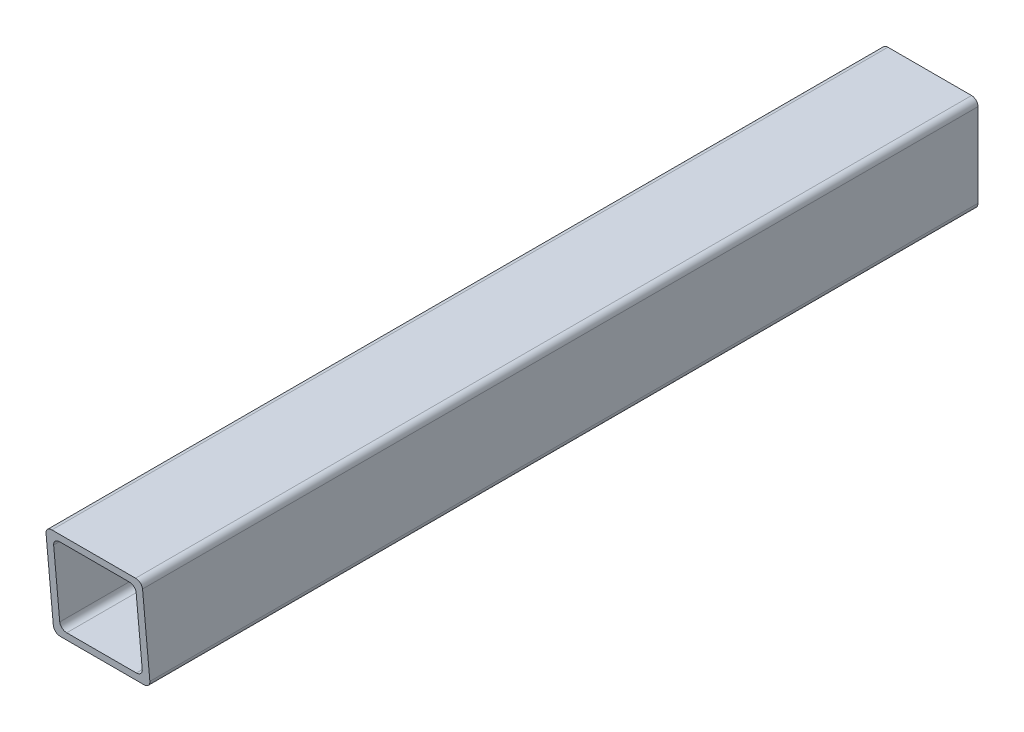
SolidWorks part; units mm, degrees
material "ASTM A500 Grade B Steel"
ref_plane "Front Plane" through (0, 0, 0) normal (0, 0, 1) x (1, 0, 0)
ref_plane "Top Plane" through (0, 0, 0) normal (0, 1, 0) x (1, 0, 0)
ref_plane "Right Plane" through (0, 0, 0) normal (1, 0, 0) x (0, 0, -1)
sketch "Sketch1" plane through (0, 0, 0) normal (0, 0, 1) x (1, 0, 0)
  line L0 (5.3086, -2.7686) -> (32.7914, -2.7686)
  line L1 (2.54, 0) -> (35.56, 0)
  line L2 (0, -2.54) -> (0, -35.56)
  line L3 (2.54, -38.1) -> (35.56, -38.1)
  line L4 (38.1, -2.54) -> (38.1, -35.56)
  line L5 (35.3314, -5.3086) -> (35.3314, -32.7914)
  line L6 (5.3086, -35.3314) -> (32.7914, -35.3314)
  line L7 (2.7686, -5.3086) -> (2.7686, -32.7914)
  line L8 (0, 0) -> (0, -38.1) construction
  line L9 (0, -38.1) -> (38.1, -38.1) construction
  line L10 (38.1, 0) -> (38.1, -38.1) construction
  line L11 (2.7686, -2.7686) -> (2.7686, -35.3314) construction
  line L12 (2.7686, -35.3314) -> (35.3314, -35.3314) construction
  line L13 (35.3314, -2.7686) -> (35.3314, -35.3314) construction
  line L14 (2.7686, -2.7686) -> (35.3314, -2.7686) construction
  line L15 (0, 0) -> (38.1, 0) construction
  arc A0 (0, -35.56) -> (2.54, -38.1) centre (2.54, -35.56) ccw
  arc A1 (38.1, -35.56) -> (35.56, -38.1) centre (35.56, -35.56) cw
  arc A2 (2.7686, -32.7914) -> (5.3086, -35.3314) centre (5.3086, -32.7914) ccw
  arc A3 (32.7914, -35.3314) -> (35.3314, -32.7914) centre (32.7914, -32.7914) ccw
  arc A4 (35.3314, -5.3086) -> (32.7914, -2.7686) centre (32.7914, -5.3086) ccw
  arc A5 (38.1, -2.54) -> (35.56, 0) centre (35.56, -2.54) ccw
  arc A6 (0, -2.54) -> (2.54, 0) centre (2.54, -2.54) cw
  arc A7 (5.3086, -2.7686) -> (2.7686, -5.3086) centre (5.3086, -5.3086) ccw
  point P12 (0, -38.1)
  dimension "D4" = 2.54
  dimension "D3" = 2.7686
extrude "Boss-Extrude1" add sketch "Sketch1" along normal blind 330
sketch "Sketch2" plane through (38.1, 0, 0) normal (1, 0, 0) x (0, 0, -1)
  line L0 (-330, 0) -> (-326.6667, -38.1)
  line L1 (-330, -38.1) -> (0, -38.1) construction
  line L5 (-330, 0) -> (-330, -38.1)
  line L6 (-326.6667, -38.1) -> (-330, -38.1)
  dimension "D1" = 5
extrude "Cut-Extrude1" cut sketch "Sketch2" against normal through all
